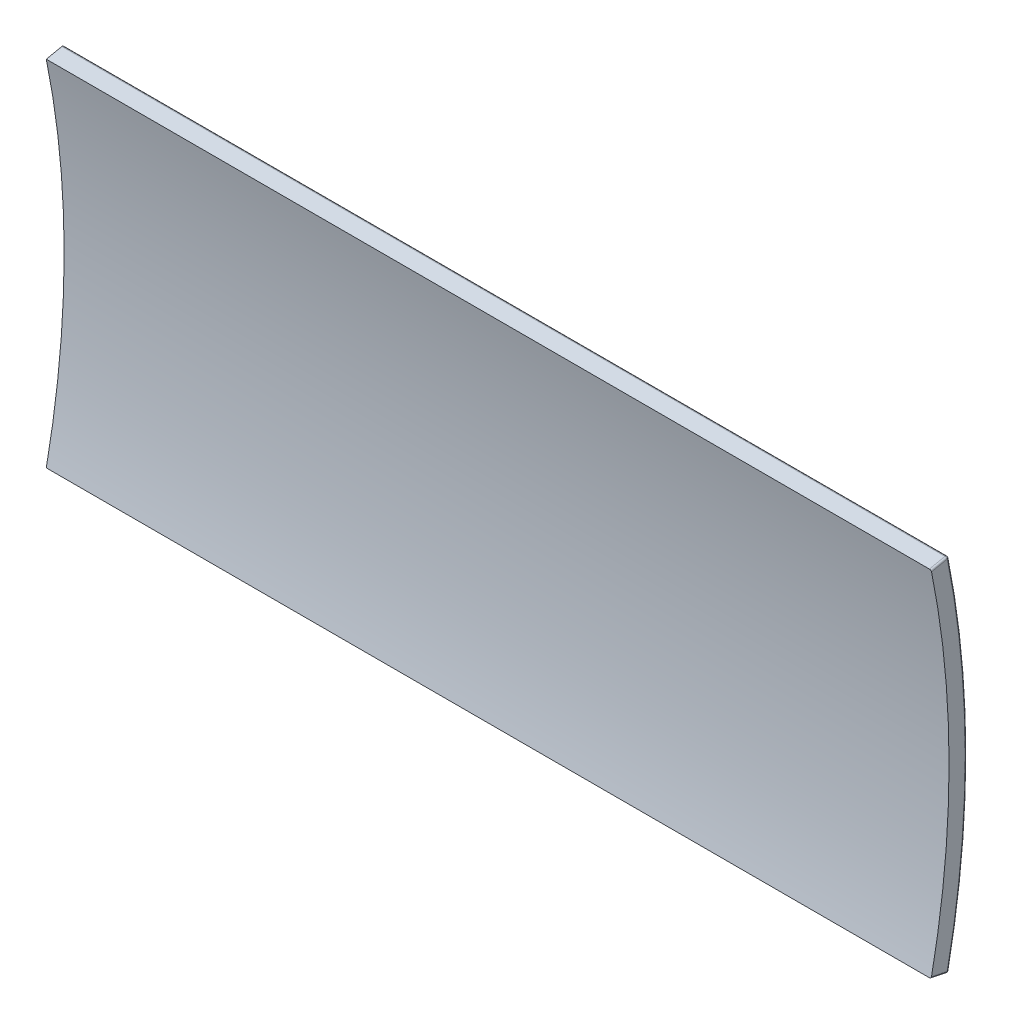
SolidWorks part; units mm, degrees
ref_plane "Front Plane" through (0, 0, 0) normal (0, 0, 1) x (1, 0, 0)
ref_plane "Top Plane" through (0, 0, 0) normal (0, 1, 0) x (1, 0, 0)
ref_plane "Right Plane" through (0, 0, 0) normal (1, 0, 0) x (0, 0, -1)
sketch "airflap" plane through (0, 0, 0) normal (1, 0, 0) x (0, 0, -1)
  line L0 (0, 0) -> (0, 50) construction
  line L1 (0, 0) -> (0, -50) construction
  line L2 (49.9696, 10.2) -> (48.9898, 10)
  line L3 (-48.9898, -10) -> (48.9898, -10) construction
  line L4 (-48.9898, -10) -> (-48.9898, 10) construction
  line L5 (-48.9898, 10) -> (48.9898, 10) construction
  line L6 (48.9898, -10) -> (48.9898, 10) construction
  line L7 (-48.9898, -10) -> (48.9898, 10) construction
  line L8 (-48.9898, 10) -> (48.9898, -10) construction
  line L9 (48.9898, -10) -> (49.9696, -10.2)
  arc A0 (48.9898, 10) -> (48.9898, -10) centre (0, 0) cw
  arc A1 (49.9696, 10.2) -> (49.9696, -10.2) centre (0, 0) cw
  dimension "D2" = 20
  dimension "D3" = 50
  dimension "D4" = 51
  dimension "D1" = 50
extrude "Boss-Extrude1" add sketch "airflap" along normal blind 50
fillet "Fillet3" radius 0.1 5 edges at (50, 10.1, -49.4797) (50, -10.1, -49.4797) (25, -10.2, -49.9696) (25, 10.2, -49.9696) (50, 0, -51)
